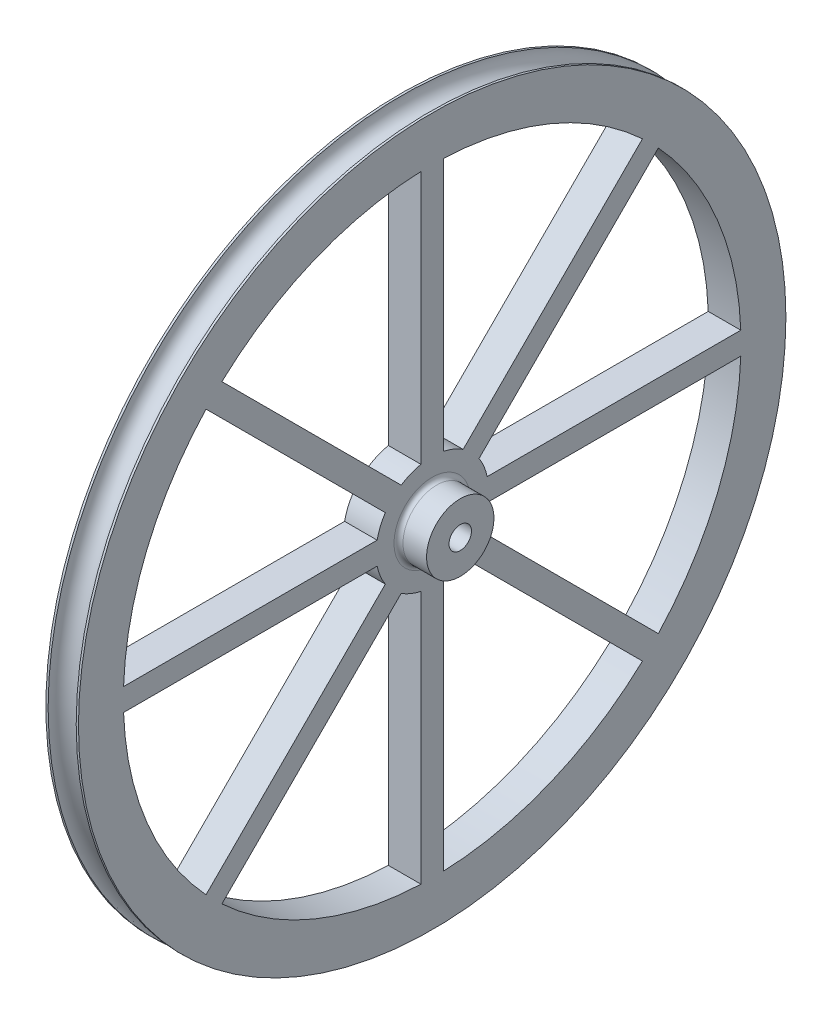
SolidWorks part; units mm, degrees
ref_plane "Front Plane" through (0, 0, 0) normal (0, 0, 1) x (1, 0, 0)
ref_plane "Top Plane" through (0, 0, 0) normal (0, 1, 0) x (1, 0, 0)
ref_plane "Right Plane" through (0, 0, 0) normal (1, 0, 0) x (0, 0, -1)
sketch "Sketch1" plane through (0, 0, 0) normal (1, 0, 0) x (0, 0, -1)
  circle A0 centre (0, 0) radius 40.005
  dimension "D1" = 80.01
extrude "Boss-Extrude1" add sketch "Sketch1" along normal blind 3.683
sketch "Sketch10" plane through (0, 0, 0) normal (0, 0, 1) x (1, 0, 0)
  line L0 (3.683, 40.005) -> (0, 40.005) construction
  line L1 (-1.0162, 0) -> (5.466, 0) construction
  line L2 (55, 0) -> (-55, 0) construction
  circle A0 centre (1.8415, 40.005) radius 1.5875
  dimension "D1" = 3.175
revolve "Cut-Revolve1" cut sketch "Sketch10" angle 360 about L1
sketch "Sketch11" plane through (3.683, 0, 0) normal (1, 0, 0) x (0, 0, -1)
  line L2 (0, -50.6508) -> (0, 43.6326) construction
  line L3 (-53.144, 0) -> (6.35, 0) construction
  line L4 (-1.27, 34.9019) -> (-1.27, 6.2217)
  line L5 (1.27, 34.9019) -> (1.27, 6.2217)
  line L6 (23.7813, 25.5774) -> (3.5014, 5.2974)
  line L7 (25.5774, 23.7813) -> (5.2974, 3.5014)
  line L8 (34.9019, 1.27) -> (6.2217, 1.27)
  line L9 (34.9019, -1.27) -> (6.2217, -1.27)
  line L10 (25.5774, -23.7813) -> (5.2974, -3.5014)
  line L11 (23.7813, -25.5774) -> (3.5014, -5.2974)
  line L12 (1.27, -34.9019) -> (1.27, -6.2217)
  line L13 (-1.27, -34.9019) -> (-1.27, -6.2217)
  line L14 (-23.7813, -25.5774) -> (-3.5014, -5.2974)
  line L15 (-25.5774, -23.7813) -> (-5.2974, -3.5014)
  line L16 (-34.9019, -1.27) -> (-6.2217, -1.27)
  line L17 (-34.9019, 1.27) -> (-6.2217, 1.27)
  line L18 (-25.5774, 23.7813) -> (-5.2974, 3.5014)
  line L19 (-23.7813, 25.5774) -> (-3.5014, 5.2974)
  arc A2 (5.2974, -3.5014) -> (6.2217, -1.27) centre (0, 0) ccw
  arc A3 (-25.5774, 23.7813) -> (-34.9019, 1.27) centre (0, 0) ccw
  arc A4 (23.7813, 25.5774) -> (1.27, 34.9019) centre (0, 0) ccw
  arc A5 (-1.27, 34.9019) -> (-23.7813, 25.5774) centre (0, 0) ccw
  arc A6 (34.9019, 1.27) -> (25.5774, 23.7813) centre (0, 0) ccw
  arc A7 (25.5774, -23.7813) -> (34.9019, -1.27) centre (0, 0) ccw
  arc A8 (1.27, -34.9019) -> (23.7813, -25.5774) centre (0, 0) ccw
  arc A9 (-23.7813, -25.5774) -> (-1.27, -34.9019) centre (0, 0) ccw
  arc A10 (-34.9019, -1.27) -> (-25.5774, -23.7813) centre (0, 0) ccw
  arc A11 (1.27, -6.2217) -> (3.5014, -5.2974) centre (0, 0) ccw
  arc A12 (-3.5014, -5.2974) -> (-1.27, -6.2217) centre (0, 0) ccw
  arc A13 (-6.2217, -1.27) -> (-5.2974, -3.5014) centre (0, 0) ccw
  arc A14 (-5.2974, 3.5014) -> (-6.2217, 1.27) centre (0, 0) ccw
  arc A15 (-1.27, 6.2217) -> (-3.5014, 5.2974) centre (0, 0) ccw
  arc A16 (3.5014, 5.2974) -> (1.27, 6.2217) centre (0, 0) ccw
  arc A17 (6.2217, 1.27) -> (5.2974, 3.5014) centre (0, 0) ccw
  point P43 (0, 0)
  dimension "D1" = 12.7
  dimension "D2" = 69.85
  dimension "D3" = 2.54
  dimension "D4" = 1.27
  dimension "D5" = 8
extrude "Cut-Extrude3" cut sketch "Sketch11" against normal through all
sketch "Sketch12" plane through (3.683, 0, 0) normal (1, 0, 0) x (0, 0, -1)
  circle A0 centre (0, 0) radius 1.27
  dimension "D1" = 2.54
extrude "Cut-Extrude4" cut sketch "Sketch12" against normal through all
sketch "Sketch13" plane through (3.683, 0, 0) normal (1, 0, 0) x (0, 0, -1)
  circle A0 centre (0, 0) radius 3.81
  circle A1 centre (0, 0) radius 1.27
  dimension "D1" = 7.62
  dimension "D2" = 2.54
extrude "Boss-Extrude2" add sketch "Sketch13" along normal blind 3.175
fillet "Fillet1" radius 0.508 1 edges at (3.683, 0, -3.81)
